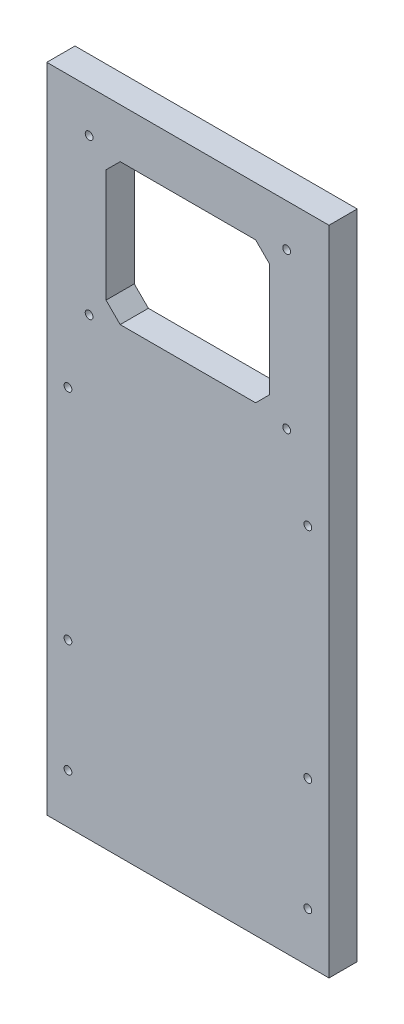
SolidWorks part; units mm, degrees
ref_plane "Front Plane" through (0, 0, 0) normal (0, 0, 1) x (1, 0, 0)
ref_plane "Top Plane" through (0, 0, 0) normal (0, 1, 0) x (1, 0, 0)
ref_plane "Right Plane" through (0, 0, 0) normal (1, 0, 0) x (0, 0, -1)
sketch "Sketch1" plane through (0, 0, 0) normal (0, 0, 1) x (1, 0, 0)
  line L0 (-50, 115.5) -> (-50, 100.5)
  line L1 (-50, -115.5) -> (50, -115.5)
  line L2 (-50, -115.5) -> (-50, 115.5)
  line L3 (-50, 115.5) -> (50, 115.5)
  line L4 (50, -115.5) -> (50, 115.5)
  line L5 (-50, -115.5) -> (50, 115.5) construction
  line L6 (-50, 115.5) -> (50, -115.5) construction
  line L7 (-50, 100.5) -> (-35, 100.5)
  line L8 (0, 115.5) -> (0, -115.5)
  line L9 (-35, 100.5) -> (-35, 45.52)
  line L10 (0, -115.5) -> (-42.5, -115.5)
  line L11 (-42.5, -115.5) -> (-42.5, -98)
  line L12 (-42.5, -98) -> (-42.5, -58)
  line L13 (-42.5, -58) -> (-42.5, 19.5)
  line L15 (-29, 48.01) -> (29, 48.01)
  line L16 (-29, 48.01) -> (-29, 98.01)
  line L17 (-29, 98.01) -> (29, 98.01)
  line L18 (29, 48.01) -> (29, 98.01)
  line L19 (-29, 48.01) -> (29, 98.01) construction
  line L20 (-29, 98.01) -> (29, 48.01) construction
  circle A0 centre (-35, 100.5) radius 1.375
  circle A4 centre (-35, 45.52) radius 1.375
  circle A8 centre (35, 45.52) radius 1.375
  circle A9 centre (35, 100.5) radius 1.375
  circle A10 centre (-42.5, 19.5) radius 1.375
  circle A11 centre (-42.5, -58) radius 1.375
  circle A12 centre (-42.5, -98) radius 1.375
  circle A13 centre (42.5, -58) radius 1.375
  circle A14 centre (42.5, 19.5) radius 1.375
  circle A15 centre (42.5, -98) radius 1.375
  point P0 (0, 0)
  point P30 (0, 73.01)
  dimension "D3" = 15
  dimension "D5" = 7.5
  dimension "D1" = 100
  dimension "D2" = 15
  dimension "D4" = 231
  dimension "D6" = 58
  dimension "D7" = 50
extrude "Boss-Extrude1" add sketch "Sketch1" along normal blind 10 contours A12 A11 A10 L1 L8 L3 L0 A0 A4 L2 | L3 L8 L1 L4 A14 A9 A8 A13 A15 region at (-26.4691, -10.5182, 0) region at (26.4691, -10.5182, 0)
chamfer "Chamfer1" distance 5 angle 45 4 edges at (-29, 48.01, 5) (29, 48.01, 5) (29, 98.01, 5) (-29, 98.01, 5)
